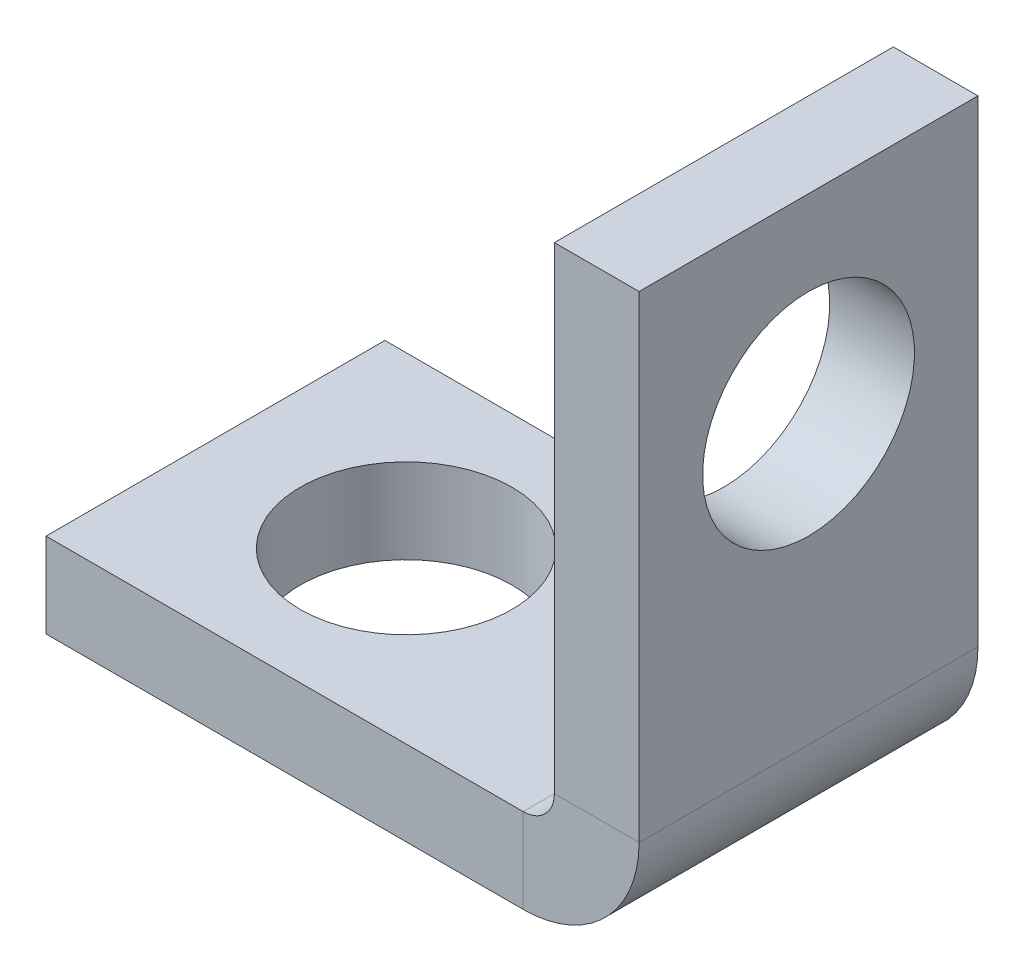
SolidWorks part; units mm, degrees
note: The reader was unsure of these and kept them because the rebuilt part matched: thickness of "Base-Flange1", "Edge-Flange1", "Sheet-Metal1", "Sheet-Metal2"; flange length of "Edge-Flange1".
material "2024-O"
ref_plane "Front Plane" through (0, 0, 0) normal (0, 0, 1) x (1, 0, 0)
ref_plane "Top Plane" through (0, 0, 0) normal (0, 1, 0) x (1, 0, 0)
ref_plane "Right Plane" through (0, 0, 0) normal (1, 0, 0) x (0, 0, -1)
sketch "Sketch1" plane through (0, 0, 0) normal (0, 1, 0) x (1, 0, 0)
  line L0 (-7, 0) -> (-2.5, 0) construction
  line L1 (7, -4) -> (-7, -4)
  line L2 (7, -4) -> (7, 4)
  line L3 (7, 4) -> (-7, 4)
  line L4 (-7, -4) -> (-7, 4)
  line L5 (7, -4) -> (-7, 4) construction
  line L6 (7, 4) -> (-7, -4) construction
  circle A0 centre (-2.5, 0) radius 2.5
  point P0 (0, 0)
  dimension "D3" = 5
  dimension "D1" = 8
  dimension "D2" = 14
  dimension "D4" = 4.5
base flange "Base-Flange1" sketch "Sketch1" thickness 2 reverse thickness direction no parameters "D1"=0.7366
edge flange "Edge-Flange1" sketch "Sketch8" flange angle 90 flange length 14 flange position material inside bend radius 0.7366 thickness 2 relief rectangular parameters "D6"=10
sketch "Sketch8" plane through (7, 0, 0) normal (1, 0, 0) x (0, 0, -1)
  line L0 (-4, 0) -> (4, 0) construction
  line L1 (-4, 0) -> (4, 0)
  line L2 (-4, 0) -> (-4, 12)
  line L3 (-4, 12) -> (4, 12)
  line L4 (4, 12) -> (4, 0)
  line L5 (0, 12) -> (0, 7.5) construction
  circle A0 centre (0, 7.5) radius 2.5
  dimension "D1" = 5
  dimension "D2" = 4.5
bend "EdgeBend1" bend radius 0.7366 bend angle 90 parameters "D5"=1
sketch "Bend-Lines1" [suppressed] plane through (0, 0, 0) normal (0, 1, 0) x (1, 0, 0)
sketch "Bounding-Box1" [suppressed] plane through (0, 0, 0) normal (0, 1, 0) x (1, 0, 0)
sheet metal parameters "Sheet-Metal1" thickness 2 parameters "D1"=0.7366
flat pattern "Flat-Pattern1" [suppressed]
sketch "Bend-Lines2" plane through (0, 0, 0) normal (0, 1, 0) x (1, 0, 0)
sketch3d "Bounding-Box2" [suppressed]
  line L0 (-7, -4, 0) -> (7, -4, 0) construction
  line L1 (-7, 4, 0) -> (7, 4, 0) construction
  line L2 (-7, -4, 0) -> (-7, 4, 0) construction
  line L3 (7, -4, 0) -> (7, 4, 0) construction
sheet metal parameters "Sheet-Metal2" thickness 2 parameters "D1"=0.7366, "D7"=1
flat pattern "Flat-Pattern1"
sketch "Bend-Lines2" plane through (0, 0, 0) normal (0, 1, 0) x (1, 0, 0)
  line L0 (5.6273, -4) -> (5.6273, 4) construction
  line L1 (5.6273, -4) -> (5.6273, 4) construction
sketch3d "Bounding-Box2" [suppressed]
  line L0 (18.2546, -4, 0) -> (-7, -4, 0) construction
  line L1 (18.2546, 4, 0) -> (-7, 4, 0) construction
  line L2 (18.2546, -4, 0) -> (18.2546, 4, 0) construction
  line L3 (-7, -4, 0) -> (-7, 4, 0) construction
bend of the flat pattern "Flatten-<EdgeBend1>1"
